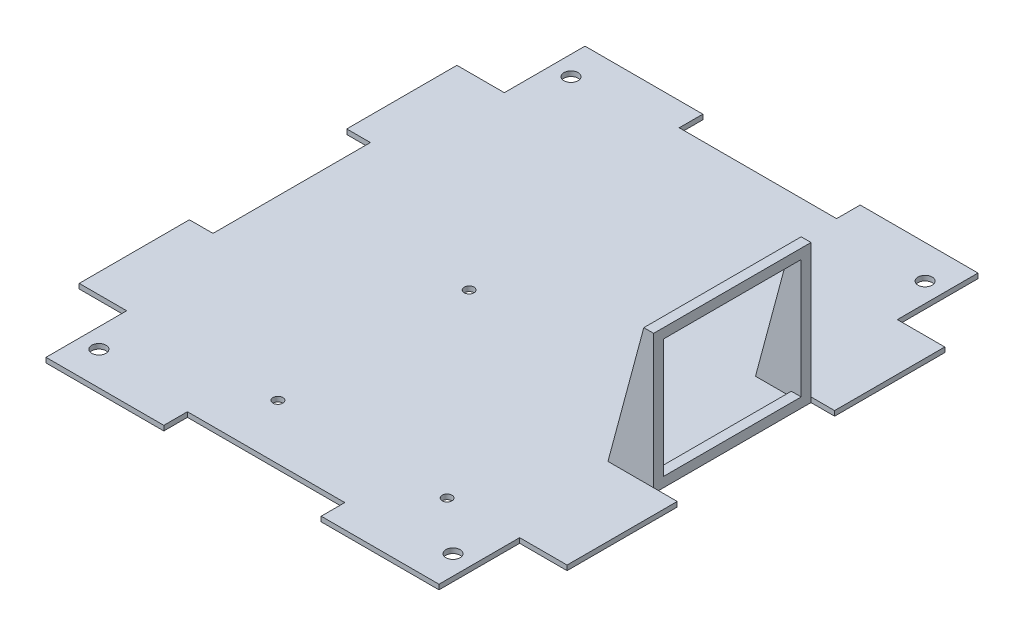
SolidWorks part; units mm, degrees
ref_plane "Front Plane" through (0, 0, 0) normal (0, 0, 1) x (1, 0, 0)
ref_plane "Top Plane" through (0, 0, 0) normal (0, 1, 0) x (1, 0, 0)
ref_plane "Right Plane" through (0, 0, 0) normal (1, 0, 0) x (0, 0, -1)
sketch "Sketch1" plane through (0, 0, 0) normal (0, 1, 0) x (1, 0, 0)
  line L0 (-25.4, 86.995) -> (-63.4314, 86.995)
  line L1 (-88.9, -101.6) -> (88.9, -101.6) construction
  line L2 (101.6, -88.9) -> (101.6, 88.9) construction
  line L3 (88.9, 101.6) -> (-88.9, 101.6) construction
  line L4 (-78.74, -60.96) -> (-63.4314, -60.96)
  line L5 (-63.4314, -60.96) -> (-63.4314, -86.995)
  line L6 (-63.4314, -86.995) -> (-25.4, -86.995)
  line L7 (63.4314, -86.995) -> (63.4314, -60.96)
  line L8 (63.4314, -60.96) -> (78.74, -60.96)
  line L9 (78.74, -60.96) -> (78.74, -25.4)
  line L10 (78.74, 60.96) -> (63.4314, 60.96)
  line L11 (63.4314, 60.96) -> (63.4314, 86.995)
  line L12 (63.4314, 86.995) -> (25.4, 86.995)
  line L13 (-63.4314, 86.995) -> (-63.4314, 60.96)
  line L14 (-63.4314, 60.96) -> (-78.74, 60.96)
  line L15 (-78.74, 60.96) -> (-78.74, 25.4)
  line L16 (-78.74, -25.4) -> (-78.74, -60.96)
  line L17 (-78.74, -25.4) -> (-71.12, -25.4)
  line L19 (-78.74, 25.4) -> (-71.12, 25.4)
  line L20 (-71.12, -25.4) -> (-71.12, 25.4)
  line L22 (-25.4, 86.995) -> (-25.4, 79.375)
  line L23 (-25.4, 79.375) -> (25.4, 79.375)
  line L24 (25.4, 86.995) -> (25.4, 79.375)
  line L25 (78.74, 25.4) -> (71.12, 25.4)
  line L27 (78.74, -25.4) -> (71.12, -25.4)
  line L28 (71.12, 25.4) -> (71.12, -25.4)
  line L30 (25.4, -86.995) -> (25.4, -79.375)
  line L31 (25.4, -79.375) -> (-25.4, -79.375)
  line L32 (-25.4, -86.995) -> (-25.4, -79.375)
  line L33 (78.74, 25.4) -> (78.74, 60.96)
  line L34 (25.4, -86.995) -> (63.4314, -86.995)
  line L35 (-101.6, 88.9) -> (-101.6, -88.9) construction
  arc A0 (88.9, -101.6) -> (101.6, -88.9) centre (88.9, -88.9) ccw construction
  arc A1 (-101.6, -88.9) -> (-88.9, -101.6) centre (-88.9, -88.9) ccw construction
  arc A2 (101.6, 88.9) -> (88.9, 101.6) centre (88.9, 88.9) ccw construction
  arc A3 (-101.6, 88.9) -> (-88.9, 101.6) centre (-88.9, 88.9) cw construction
  circle A4 centre (-57.15, 76.2) radius 2.286
  circle A5 centre (57.15, 76.2) radius 2.286
  circle A6 centre (57.15, -76.2) radius 2.286
  circle A7 centre (-57.15, -76.2) radius 2.286
  point P3 (0, 101.6)
  point P5 (101.6, 0)
  point P13 (101.6, 101.6)
  point P16 (-101.6, 101.6)
  point P38 (-71.12, 0)
  point P55 (0, -79.375)
  point P56 (0, 79.375)
  point P57 (71.12, 0)
  dimension "D2" = 12.7
  dimension "D11" = 4.572
  dimension "D8" = 44.45
  dimension "D1" = 203.2
  dimension "D3" = 203.2
  dimension "D4" = 22.86
  dimension "D5" = 15.3086
  dimension "D6" = 35.56
  dimension "D7" = 173.99
  dimension "D12" = 50.8
  dimension "D13" = 25.4
  dimension "D14" = 44.45
  dimension "D15" = 25.4
  dimension "D18" = 7.62
extrude "Main Body" add sketch "Sketch1" along normal blind 1.5875
sketch "Sketch2" plane through (0, 1.5875, 0) normal (0, 1, 0) x (1, 0, 0)
  line L0 (71.12, -25.4) -> (67.945, -25.4)
  line L1 (67.945, -25.4) -> (67.945, 25.4)
  line L2 (67.945, 25.4) -> (71.12, 25.4)
  line L28 (-78.74, -25.4) -> (-78.74, -60.96)
  line L29 (-78.74, -60.96) -> (-63.4314, -60.96)
  line L30 (-63.4314, -60.96) -> (-63.4314, -86.995)
  line L31 (-63.4314, -86.995) -> (-25.4, -86.995)
  line L32 (-25.4, -86.995) -> (-25.4, -79.375)
  line L33 (-25.4, -79.375) -> (25.4, -79.375)
  line L34 (25.4, -79.375) -> (25.4, -86.995)
  line L35 (25.4, -86.995) -> (63.4314, -86.995)
  line L36 (63.4314, -86.995) -> (63.4314, -60.96)
  line L37 (63.4314, -60.96) -> (78.74, -60.96)
  line L38 (78.74, -60.96) -> (78.74, -25.4)
  line L39 (78.74, -25.4) -> (71.12, -25.4)
  line L40 (71.12, -25.4) -> (71.12, 25.4)
  line L41 (71.12, 25.4) -> (78.74, 25.4)
  line L42 (78.74, 25.4) -> (78.74, 60.96)
  line L43 (78.74, 60.96) -> (63.4314, 60.96)
  line L44 (63.4314, 60.96) -> (63.4314, 86.995)
  line L45 (63.4314, 86.995) -> (25.4, 86.995)
  line L46 (25.4, 86.995) -> (25.4, 79.375)
  line L47 (25.4, 79.375) -> (-25.4, 79.375)
  line L48 (-25.4, 79.375) -> (-25.4, 86.995)
  line L49 (-25.4, 86.995) -> (-63.4314, 86.995)
  line L50 (-63.4314, 86.995) -> (-63.4314, 60.96)
  line L51 (-63.4314, 60.96) -> (-78.74, 60.96)
  line L52 (-78.74, 60.96) -> (-78.74, 25.4)
  line L53 (-78.74, 25.4) -> (-71.12, 25.4)
  line L54 (-71.12, 25.4) -> (-71.12, -25.4)
  line L55 (-71.12, -25.4) -> (-78.74, -25.4)
  line L56 (-78.74, -25.4) -> (-78.74, -60.96)
  line L57 (-78.74, -60.96) -> (-63.4314, -60.96)
  line L58 (-63.4314, -60.96) -> (-63.4314, -86.995)
  line L59 (-63.4314, -86.995) -> (-25.4, -86.995)
  line L60 (-25.4, -86.995) -> (-25.4, -79.375)
  line L61 (-25.4, -79.375) -> (25.4, -79.375)
  line L62 (25.4, -79.375) -> (25.4, -86.995)
  line L63 (25.4, -86.995) -> (63.4314, -86.995)
  line L64 (63.4314, -86.995) -> (63.4314, -60.96)
  line L65 (63.4314, -60.96) -> (78.74, -60.96)
  line L66 (78.74, -60.96) -> (78.74, -25.4)
  line L67 (78.74, -25.4) -> (71.12, -25.4)
  line L68 (71.12, -25.4) -> (71.12, 25.4)
  line L69 (71.12, 25.4) -> (78.74, 25.4)
  line L70 (78.74, 25.4) -> (78.74, 60.96)
  line L71 (78.74, 60.96) -> (63.4314, 60.96)
  line L72 (63.4314, 60.96) -> (63.4314, 86.995)
  line L73 (63.4314, 86.995) -> (25.4, 86.995)
  line L74 (25.4, 86.995) -> (25.4, 79.375)
  line L75 (25.4, 79.375) -> (-25.4, 79.375)
  line L76 (-25.4, 79.375) -> (-25.4, 86.995)
  line L77 (-25.4, 86.995) -> (-63.4314, 86.995)
  line L78 (-63.4314, 86.995) -> (-63.4314, 60.96)
  line L79 (-63.4314, 60.96) -> (-78.74, 60.96)
  line L80 (-78.74, 60.96) -> (-78.74, 25.4)
  line L81 (-78.74, 25.4) -> (-71.12, 25.4)
  line L82 (-71.12, 25.4) -> (-71.12, -25.4)
  line L83 (-71.12, -25.4) -> (-78.74, -25.4)
  line M44 (71.12, -25.4) -> (71.12, 25.4)
  dimension "D2" = 3.175
  dimension "D1" = 0
extrude "Boss-Extrude1" add sketch "Sketch2" along normal blind 43.18 contours L2 L1 L0 M44 region at (69.5325, 1.5875, 0)
sketch "Sketch3" plane through (71.12, 0, 0) normal (1, 0, 0) x (0, 0, -1)
  line L1 (-22.225, 3.175) -> (22.225, 3.175)
  line L2 (-22.225, 3.175) -> (-22.225, 41.5925)
  line L3 (-22.225, 41.5925) -> (22.225, 41.5925)
  line L4 (22.225, 3.175) -> (22.225, 41.5925)
  line L5 (-22.225, 3.175) -> (22.225, 41.5925) construction
  line L6 (-25.4, 0) -> (25.4, 0)
  line L7 (25.4, 0) -> (25.4, 1.5875)
  line L8 (25.4, 1.5875) -> (25.4, 44.7675)
  line L9 (25.4, 44.7675) -> (-25.4, 44.7675)
  line L10 (-25.4, 44.7675) -> (-25.4, 1.5875)
  line L11 (-25.4, 1.5875) -> (-25.4, 0)
  line L12 (-25.4, 0) -> (25.4, 0)
  line L13 (25.4, 0) -> (25.4, 1.5875)
  line L14 (25.4, 1.5875) -> (25.4, 44.7675)
  line L15 (25.4, 44.7675) -> (-25.4, 44.7675)
  line L16 (-25.4, 44.7675) -> (-25.4, 1.5875)
  line L17 (-25.4, 1.5875) -> (-25.4, 0)
  line L18 (-22.225, 41.5925) -> (22.225, 3.175) construction
  point P2 (0, 22.3837)
  dimension "D2" = 3.175
  dimension "D3" = 3.175
  dimension "D4" = 3.175
  dimension "D5" = 3.175
  dimension "D1" = 0
extrude "Cut-Extrude1" cut sketch "Sketch3" against normal up to next contours L2 L3 L4 L1
sketch "Sketch4" plane through (0, 0, -25.4) normal (0, 0, -1) x (-1, 0, 0)
  line L0 (-67.945, 44.7675) -> (-56.375, 1.5875)
  line L1 (-63.4314, 1.5875) -> (-25.4, 1.5875) construction
  line L2 (-67.945, 1.5875) -> (-56.375, 1.5875)
  line L4 (-71.12, 1.5875) -> (-67.945, 1.5875)
  line L5 (-67.945, 1.5875) -> (-67.945, 44.7675)
  line L6 (-67.945, 44.7675) -> (-71.12, 44.7675)
  line L7 (-71.12, 44.7675) -> (-71.12, 1.5875)
  line L8 (-71.12, 1.5875) -> (-67.945, 1.5875)
  line L9 (-67.945, 1.5875) -> (-67.945, 44.7675)
  line L10 (-67.945, 44.7675) -> (-71.12, 44.7675)
  line L11 (-71.12, 44.7675) -> (-71.12, 1.5875)
  line M8 (-67.945, 1.5875) -> (-67.945, 44.7675)
  dimension "D2" = 15
  dimension "D1" = 0
extrude "Boss-Extrude2" add sketch "Sketch4" against normal blind 3.175 contours L2 L0 M8 region at (64.0883, 15.9808, -25.4)
mirror "Mirror1" about plane through (0, 0, 0) normal (0, 0, 1) of "Boss-Extrude2"
sketch "Sketch5" plane through (0, 1.5875, 0) normal (0, 1, 0) x (1, 0, 0)
  line L34 (56.375, -25.4) -> (56.375, -22.225)
  line L35 (56.375, -22.225) -> (67.945, -22.225)
  line L36 (67.945, -22.225) -> (67.945, 22.225)
  line L37 (67.945, 22.225) -> (56.375, 22.225)
  line L38 (56.375, 22.225) -> (56.375, 25.4)
  line L39 (56.375, 25.4) -> (71.12, 25.4)
  line L40 (71.12, 25.4) -> (78.74, 25.4)
  line L41 (78.74, 25.4) -> (78.74, 60.96)
  line L42 (78.74, 60.96) -> (63.4314, 60.96)
  line L43 (63.4314, 60.96) -> (63.4314, 86.995)
  line L44 (63.4314, 86.995) -> (25.4, 86.995)
  line L45 (25.4, 86.995) -> (25.4, 79.375)
  line L46 (25.4, 79.375) -> (-25.4, 79.375)
  line L47 (-25.4, 79.375) -> (-25.4, 86.995)
  line L48 (-25.4, 86.995) -> (-63.4314, 86.995)
  line L49 (-63.4314, 86.995) -> (-63.4314, 60.96)
  line L50 (-63.4314, 60.96) -> (-78.74, 60.96)
  line L51 (-78.74, 60.96) -> (-78.74, 25.4)
  line L52 (-78.74, 25.4) -> (-71.12, 25.4)
  line L53 (-71.12, 25.4) -> (-71.12, -25.4)
  line L54 (-71.12, -25.4) -> (-78.74, -25.4)
  line L55 (-78.74, -25.4) -> (-78.74, -60.96)
  line L56 (-78.74, -60.96) -> (-63.4314, -60.96)
  line L57 (-63.4314, -60.96) -> (-63.4314, -86.995)
  line L58 (-63.4314, -86.995) -> (-25.4, -86.995)
  line L59 (-25.4, -86.995) -> (-25.4, -79.375)
  line L60 (-25.4, -79.375) -> (25.4, -79.375)
  line L61 (25.4, -79.375) -> (25.4, -86.995)
  line L62 (25.4, -86.995) -> (63.4314, -86.995)
  line L63 (63.4314, -86.995) -> (63.4314, -60.96)
  line L64 (63.4314, -60.96) -> (78.74, -60.96)
  line L65 (78.74, -60.96) -> (78.74, -25.4)
  line L66 (78.74, -25.4) -> (71.12, -25.4)
  line L67 (71.12, -25.4) -> (56.375, -25.4)
  line L68 (56.375, -25.4) -> (56.375, -22.225)
  line L69 (56.375, -22.225) -> (67.945, -22.225)
  line L70 (67.945, -22.225) -> (67.945, 22.225)
  line L71 (67.945, 22.225) -> (56.375, 22.225)
  line L72 (56.375, 22.225) -> (56.375, 25.4)
  line L73 (56.375, 25.4) -> (71.12, 25.4)
  line L74 (71.12, 25.4) -> (78.74, 25.4)
  line L75 (78.74, 25.4) -> (78.74, 60.96)
  line L76 (78.74, 60.96) -> (63.4314, 60.96)
  line L77 (63.4314, 60.96) -> (63.4314, 86.995)
  line L78 (63.4314, 86.995) -> (25.4, 86.995)
  line L79 (25.4, 86.995) -> (25.4, 79.375)
  line L80 (25.4, 79.375) -> (-25.4, 79.375)
  line L81 (-25.4, 79.375) -> (-25.4, 86.995)
  line L82 (-25.4, 86.995) -> (-63.4314, 86.995)
  line L83 (-63.4314, 86.995) -> (-63.4314, 60.96)
  line L84 (-63.4314, 60.96) -> (-78.74, 60.96)
  line L85 (-78.74, 60.96) -> (-78.74, 25.4)
  line L86 (-78.74, 25.4) -> (-71.12, 25.4)
  line L87 (-71.12, 25.4) -> (-71.12, -25.4)
  line L88 (-71.12, -25.4) -> (-78.74, -25.4)
  line L89 (-78.74, -25.4) -> (-78.74, -60.96)
  line L90 (-78.74, -60.96) -> (-63.4314, -60.96)
  line L91 (-63.4314, -60.96) -> (-63.4314, -86.995)
  line L92 (-63.4314, -86.995) -> (-25.4, -86.995)
  line L93 (-25.4, -86.995) -> (-25.4, -79.375)
  line L94 (-25.4, -79.375) -> (25.4, -79.375)
  line L95 (25.4, -79.375) -> (25.4, -86.995)
  line L96 (25.4, -86.995) -> (63.4314, -86.995)
  line L97 (63.4314, -86.995) -> (63.4314, -60.96)
  line L98 (63.4314, -60.96) -> (78.74, -60.96)
  line L99 (78.74, -60.96) -> (78.74, -25.4)
  line L100 (78.74, -25.4) -> (71.12, -25.4)
  line L101 (71.12, -25.4) -> (56.375, -25.4)
  circle A0 centre (-13.97, 0.127) radius 1.5875
  circle A1 centre (40.64, 0.127) radius 1.5875
  circle A2 centre (40.64, -61.595) radius 1.5875
  circle A3 centre (-13.97, -61.595) radius 1.5875
  text T0 "<b>LIPO</b>"
  point P2 (40.64, -61.595)
  point P4 (-13.97, -61.595)
  point P6 (-13.97, 0.127)
  point P8 (40.64, 0.127)
  point P28 (10.8304, -21.1063)
  point P30 (0, 0)
  dimension "D8" = 3.175
  dimension "D9" = 3.175
  dimension "D10" = 3.175
  dimension "D11" = 3.175
  dimension "D2" = 54.61
  dimension "D3" = 61.722
  dimension "D4" = 54.61
  dimension "D5" = 61.722
  dimension "D6" = 38.1
  dimension "D7" = 25.4
  dimension "D12" = 21.59
  dimension "D13" = 28.575
  dimension "D1" = 0
extrude "Cut-Extrude2" cut sketch "Sketch5" against normal up to next contours A0 | A1 | A2 | A3
